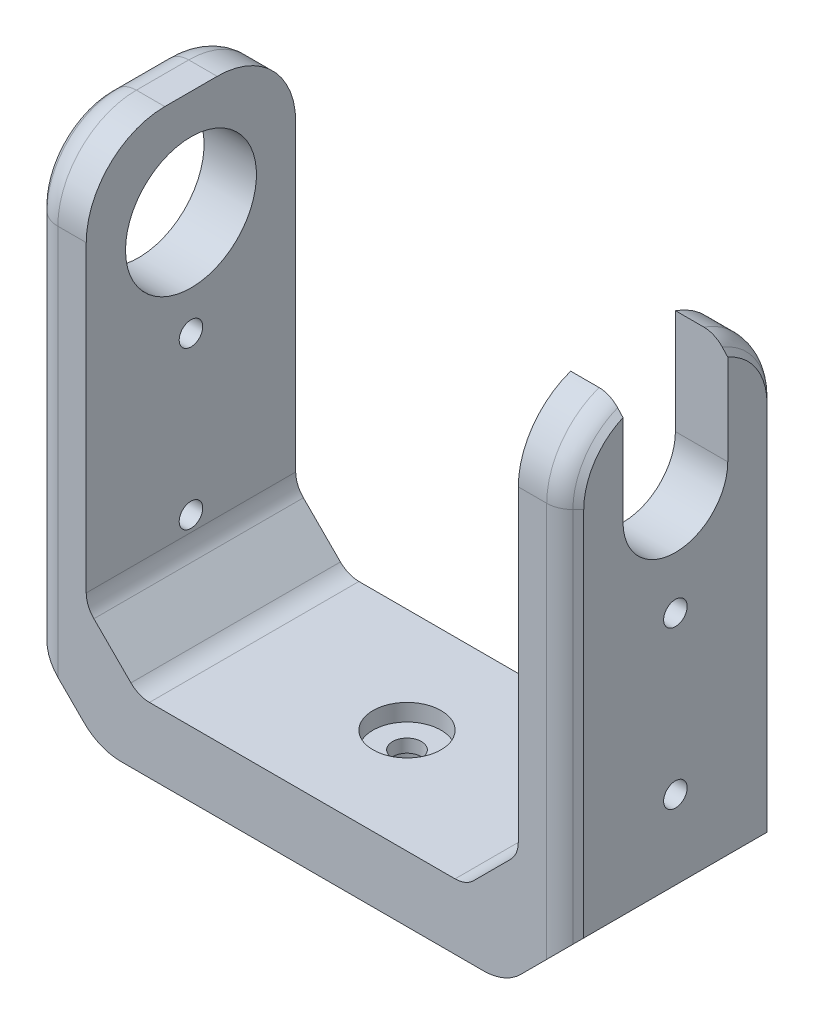
SolidWorks part; units mm, degrees
ref_plane "Front Plane" through (0, 0, 0) normal (0, 0, 1) x (1, 0, 0)
ref_plane "Top Plane" through (0, 0, 0) normal (0, 1, 0) x (1, 0, 0)
ref_plane "Right Plane" through (0, 0, 0) normal (1, 0, 0) x (0, 0, -1)
sketch "Sketch1" plane through (0, 0, 0) normal (0, 1, 0) x (1, 0, 0)
  line L0 (16.5, 8) -> (33, 16) construction
  line L1 (0, 0) -> (33, 0)
  line L2 (0, 0) -> (0, 16)
  line L3 (0, 16) -> (33, 16)
  line L4 (33, 0) -> (33, 16)
  line L5 (16.5, 8) -> (33, 0) construction
  line L6 (16.5, 8) -> (0, 16) construction
  circle A0 centre (16.5, 8) radius 2.5
  dimension "D1" = 5
  dimension "D2" = 16
  dimension "D3" = 33
extrude "Boss-Extrude1" add sketch "Sketch1" along normal blind 2.7
sketch "Sketch2" plane through (0, 2.7, 0) normal (0, 1, 0) x (1, 0, 0)
  line L1 (0, 16) -> (33, 16)
  line L2 (0, 16) -> (0, 0)
  line L3 (0, 0) -> (33, 0)
  line L4 (33, 16) -> (33, 0)
  circle A0 centre (16.5, 8) radius 1.1
  circle A2 centre (16.5, 8) radius 2.5 construction
  point P8 (0, 0)
  dimension "D1" = 2.2
extrude "Boss-Extrude2" add sketch "Sketch2" along normal blind 2.3
sketch "Sketch4" plane through (0, 0, 0) normal (-1, 0, 0) x (0, 0, 1)
  line L0 (-8, 31) -> (-16, 39) construction
  line L1 (-16, 0) -> (0, 0)
  line L2 (-16, 0) -> (-16, 39)
  line L3 (-16, 39) -> (0, 39)
  line L4 (0, 0) -> (0, 39)
  line L5 (-8, 31) -> (0, 39) construction
  line L6 (-16, 5) -> (0, 5) construction
  circle A0 centre (-8, 31) radius 5
  point P5 (-6.05, 19.9008)
  dimension "D1" = 10
  dimension "D2" = 26
  dimension "D3" = 8
extrude "Boss-Extrude3" add sketch "Sketch4" along normal blind 4
sketch "Sketch5" plane through (33, 0, 0) normal (1, 0, 0) x (0, 0, -1)
  line L0 (0, 5) -> (0, 39) construction
  line L1 (0, 39) -> (4, 39)
  line L2 (0, 39) -> (0, 0)
  line L3 (0, 0) -> (16, 0)
  line L4 (16, 39) -> (16, 0)
  line L5 (4, 31) -> (4, 39)
  line L6 (12, 31) -> (12, 39)
  line L7 (12, 39) -> (16, 39)
  arc A0 (4, 31) -> (12, 31) centre (8, 31) ccw
  dimension "D1" = 4
extrude "Boss-Extrude4" add sketch "Sketch5" along normal blind 4
fillet "Fillet1" radius 6 4 edges at (35, 39, -16) (-2, 39, -16) (35, 39, 0) (-2, 39, 0)
chamfer "Chamfer1" distance 4 angle 45 2 edges at (33, 5, -8) (0, 5, -8)
sketch "Sketch6" plane through (-4, 0, 0) normal (-1, 0, 0) x (0, 0, 1)
  line L0 (-8, 23) -> (-8, 31) construction
  circle A0 centre (-8, 23) radius 0.9
  circle A1 centre (-8, 11) radius 0.9
  point P4 (-4.8888, 10.3297)
  dimension "D1" = 1.8
  dimension "D2" = 8
  dimension "D3" = 12
extrude "Cut-Extrude1" cut sketch "Sketch6" against normal through all
chamfer "Chamfer2" distance 1 angle 45 9 edges at (37, 16.6716, -16) (37, 36.8072, -14.899) (37, 16.6716, 0) (37, 36.8072, -1.101) (-4, 16.5, 0) (-4, 16.5, -16) (-4, 37.2426, -1.7574) (-4, 37.2426, -14.2426) (-4, 39, -8)
fillet "Fillet3" radius 2 9 edges at (36, 16.6716, -16) (36, 16.6716, 0) (-3, 16.5, -16) (-3, 37.2426, -14.2426) (-3, 16.5, 0) (-3, 37.2426, -1.7574) (36, 36.8072, -14.899) (36, 36.8072, -1.101) (-3, 39, -8)
sketch "Sketch7" plane through (0, 5, 0) normal (0, 1, 0) x (1, 0, 0)
  circle A0 centre (16.5, 8) radius 2.6
  dimension "D1" = 5.2
extrude "Cut-Extrude2" cut sketch "Sketch7" against normal blind 1.3
fillet "Fillet4" radius 2 4 edges at (33, 9, -8) (29, 5, -8) (4, 5, -8) (0, 9, -8)
chamfer "Chamfer3" distance 5 angle 45 2 edges at (37, 0, -8) (-4, 0, -8)
fillet "Fillet7" radius 4 2 edges at (32, 0, -8) (1, 0, -8)
chamfer "Chamfer4" distance 0.3 angle 45 1 edges at (16.5, 0, -5.5)
